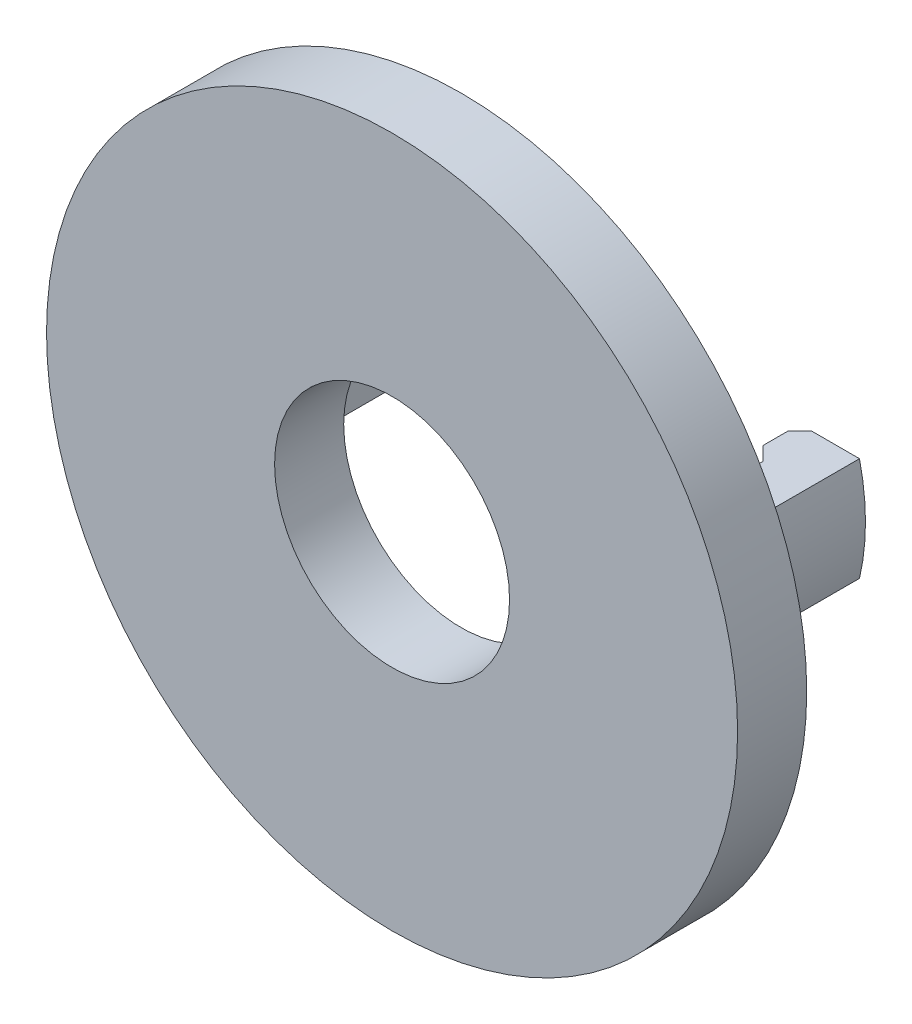
SolidWorks part; units mm, degrees
ref_plane "Front" through (0, 0, 0) normal (0, 0, 1) x (1, 0, 0)
ref_plane "Top" through (0, 0, 0) normal (0, 1, 0) x (1, 0, 0)
ref_plane "Right" through (0, 0, 0) normal (1, 0, 0) x (0, 0, -1)
sketch "Guard base" plane through (0, 0, 0) normal (0, 0, 1) x (1, 0, 0)
  circle A0 centre (0, 0) radius 25
  dimension "D1" = 50
extrude "Guard" add sketch "Guard base" along normal blind 5
sketch "Inner axle hole base" plane through (0, 0, 5) normal (0, 0, 1) x (1, 0, 0)
  circle A0 centre (0, 0) radius 8.5
  dimension "D1" = 17
extrude "Inner axle hole" cut sketch "Inner axle hole base" against normal through all
sketch "Coupling tooth base" plane through (0, 0, 0) normal (0, 1, 0) x (1, 0, 0)
  line L0 (10, 0) -> (15.5, 0) construction
  line L1 (15.5, 0) -> (15.5, 13)
  line L2 (12.5, 2.5) -> (12.5, 9) construction
  line L3 (15.5, 13) -> (12.5, 13) construction
  line L4 (12.5, 13) -> (11.5, 12) construction
  line L5 (11.5, 10) -> (12.5, 9) construction
  line L6 (16.5, 12.75) -> (16.5, 0)
  line L7 (12.75, 9.1036) -> (12.75, 2.3964)
  line L8 (12.5, 2.5) -> (10, 0) construction
  line L9 (12.75, 9.1036) -> (11.75, 10.1036)
  line L10 (11.5, 12) -> (11.5, 10) construction
  line L11 (11.75, 10.1036) -> (11.75, 11.8964)
  line L12 (15.5, 0) -> (15.5, 12.75) construction
  line L13 (15.5, 0) -> (10.3536, 0)
  line L14 (12.75, 2.3964) -> (10.3536, 0)
  line L15 (11.75, 11.8964) -> (12.6036, 12.75)
  line L16 (12.6036, 12.75) -> (15.5, 12.75)
  line L17 (15.5, 12.75) -> (25, 12.75)
  line L18 (25, 12.75) -> (25, 0)
  line L19 (25, 0) -> (15.5, 0)
  point P24 (8.5, 0)
  dimension "D2" = 1
  dimension "D3" = 4
  dimension "D4" = 13
  dimension "D5" = 4
  dimension "D6" = 0.25
  dimension "D7" = 0.25
  dimension "D8" = 0.25
  dimension "D9" = 0.25
  dimension "D10" = 225
  dimension "D11" = 5.5
  dimension "D12" = 0.25
  dimension "D13" = 135
  dimension "D14" = 0.25
  dimension "D15" = 1
  dimension "D16" = 1.5
extrude "Coupling tooth" add sketch "Coupling tooth base" along normal blind 3.75 and the other way blind 3.75 contours L16 L15 L11 L9 L7 L14 L13 L1 | L19 L6 L17 L1 region at (13.8475, 0, -6.2973) region at (16, 0, -6.375)
ref_axis "Center Z" through (0, 0, 0) along (0, 0, -1)
revolve "Circularity cut" cut sketch "Sketch6<4>" angle 360 about axis through (0, 0, 0) along (0, 0, -1) region at (20.75, 0, -6.375)
sketch "Sketch6<4>" plane through (0, 0, 0) normal (0, 1, 0) x (1, 0, 0) same geometry as "Coupling tooth base"
mirror "Coutpling teeth" about plane through (0, 0, 0) normal (1, 0, 0) of "Coupling tooth", "Circularity cut"
equation "\"mate_room\"= 0.25"
equation "\"D6@Coupling tooth base\"=\"mate_room\""
equation "\"D8@Coupling tooth base\"=\"mate_room\""
equation "\"D7@Coupling tooth base\"=\"mate_room\""
equation "\"D9@Coupling tooth base\"=\"mate_room\""
equation "\"D12@Coupling tooth base\"=\"mate_room\""
equation "\"D14@Coupling tooth base\"=\"mate_room\""
equation "\"removal_room\"= 0.75"
equation "\"D1@Inner axle hole base\" = \"small_inner_axle_diameter\""
equation "\"guard_thickness\"=5"
equation "\"spool_inner_diameter_room\"=1"
equation "\"32_92_coupling_tooth_height\"=13"
equation "\"32_92_coupling_tooth_thickness_total\"=4"
equation "\"32_92_coupling_tooth_protrusion\"=1"
equation "\"32_92_coupling_tooth_depth\"=8"
equation "\"32_92_coupling_tooth_base_thickness\"=5.5"
equation "\"D1@Guard\"=\"guard_thickness\""
equation "\"32_92_guard_diameter\"=50"
equation "\"D1@Guard base\"=\"32_92_guard_diameter\""
equation "\"D4@Coupling tooth base\"=\"32_92_coupling_tooth_height\""
equation "\"D3@Coupling tooth base\"=\"32_92_coupling_tooth_thickness_total\""
equation "\"D2@Coupling tooth base\"=\"32_92_coupling_tooth_protrusion\""
equation "\"D11@Coupling tooth base\"=\"32_92_coupling_tooth_base_thickness\""
equation "\"32_92_coupling_tooth_head_height\"=4"
equation "\"D5@Coupling tooth base\"=\"32_92_coupling_tooth_head_height\""
equation "\"32_92_spool_inner_diameter\"=32"
equation "\"32_92_spool_thickness\"=92"
equation "\"small_inner_axle_diameter\"=17"
equation "\"D16@Coupling tooth base\" = ( \"large_inner_axle_diameter\" - \"small_inner_axle_diameter\" ) / 2"
equation "\"large_inner_axle_diameter\"=20"
equation "\"D1@Coupling tooth\"=\"32_92_coupling_tooth_depth\"/2 - \"mate_room\""
equation "\"D2@Coupling tooth\"=\"32_92_coupling_tooth_depth\"/2 - \"mate_room\""
